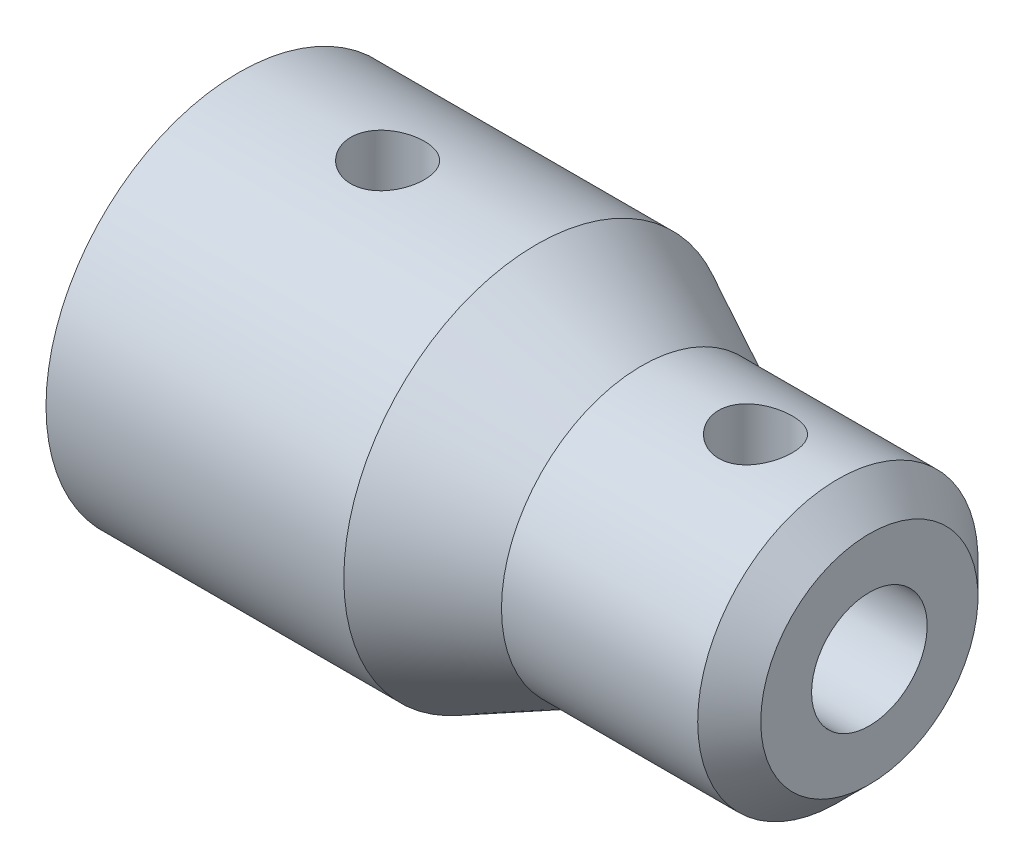
SolidWorks part; units mm, degrees
material "PLA"
ref_plane "Front Plane" through (0, 0, 0) normal (0, 0, 1) x (1, 0, 0)
ref_plane "Top Plane" through (0, 0, 0) normal (0, 1, 0) x (1, 0, 0)
ref_plane "Right Plane" through (0, 0, 0) normal (1, 0, 0) x (0, 0, -1)
sketch "Sketch1" plane through (0, 0, 0) normal (0, 1, 0) x (1, 0, 0)
  line L0 (0, 0) -> (50114.9151, 0) construction
  line L1 (0, -1002.2983) -> (0, 0) construction
  line L2 (-10.795, 3.4036) -> (0, 3.4036)
  line L3 (0, 6.985) -> (3.81, 5.08)
  line L4 (-10.795, 3.4036) -> (-10.795, 6.985)
  line L5 (-10.795, 6.985) -> (0, 6.985)
  line L8 (12.065, 5.08) -> (12.065, 2.0955)
  line L9 (0, 3.4036) -> (0, 50114.9151) construction
  line L10 (0, 3.4036) -> (1.905, 2.0955)
  line L11 (1.905, 2.0955) -> (12.065, 2.0955)
  line L12 (3.81, 5.08) -> (12.065, 5.08)
  line L13 (0.4092, 3.4036) -> (50000.4092, 3.4036) construction
  line L14 (0, 6.985) -> (50000, 6.985) construction
  dimension "D1" = 4.191
  dimension "D2" = 6.8072
  dimension "D3" = 1.905
  dimension "D4" = 13.97
  dimension "D5" = 10.16
  dimension "D6" = 22.86
  dimension "D7" = 10.795
  dimension "D8" = 3.81
revolve "Revolve1" add sketch "Sketch1" angle 360 about L0
sketch "Sketch2" plane through (0, 0, 0) normal (0, 1, 0) x (1, 0, 0)
  line L0 (0, 0) -> (50000, 0) construction
  line L1 (0, 6.985) -> (-10.795, 6.985) construction
  line L2 (-5.3975, 6.985) -> (-5.3975, 0) construction
  line L3 (7.9375, 5.08) -> (7.9375, 0) construction
  line L4 (12.065, 5.08) -> (3.81, 5.08) construction
  circle A0 centre (-5.3975, 0) radius 1.3335
  circle A1 centre (7.9375, 0) radius 1.3335
  dimension "D1" = 2.667
  dimension "D2" = 2.667
extrude "Cut-Extrude1" cut sketch "Sketch2" along normal through all
pattern_circular "CirPattern1" count 2 every 90 about axis through (-10.795, 0, 0) along (-1, 0, 0) of "Cut-Extrude1"
chamfer "Chamfer1" distance 1.143 angle 45 1 edges at (12.065, 0, 5.08)
equation "\"D2@Sketch2\"=\"D1@Sketch2\""
